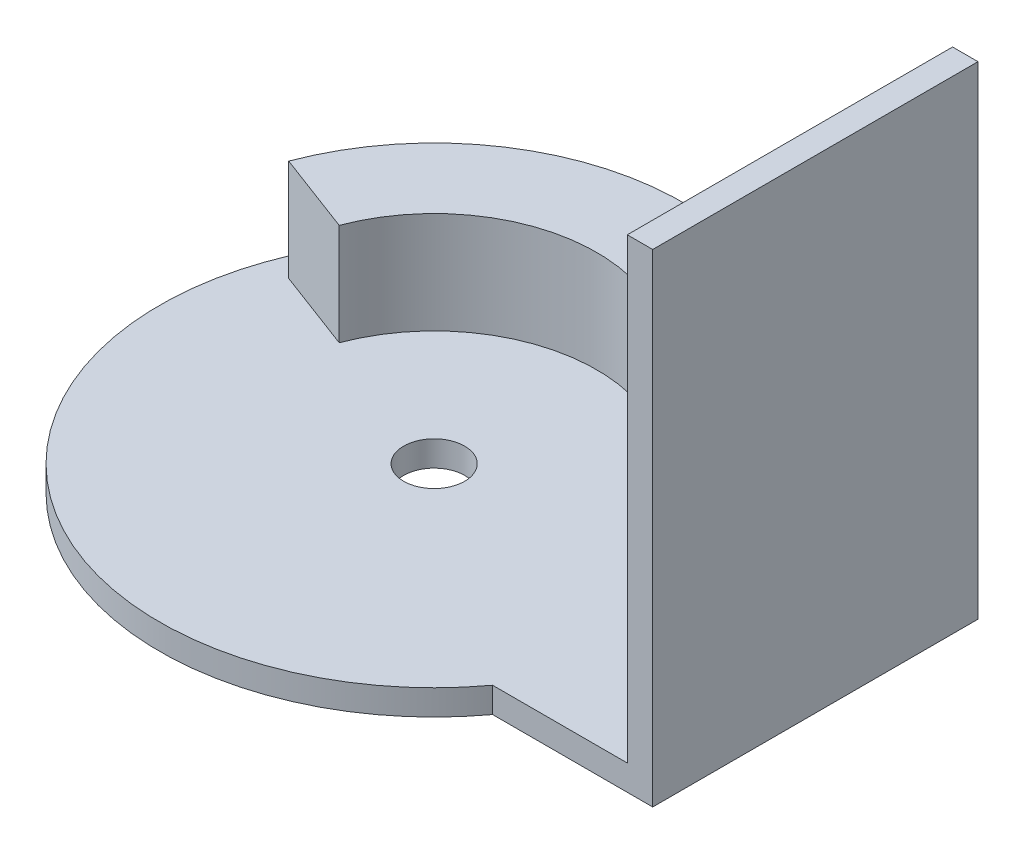
SolidWorks part; units mm, degrees
ref_plane "Front Plane" through (0, 0, 0) normal (0, 0, 1) x (1, 0, 0)
ref_plane "Top Plane" through (0, 0, 0) normal (0, 1, 0) x (1, 0, 0)
ref_plane "Right Plane" through (0, 0, 0) normal (1, 0, 0) x (0, 0, -1)
sketch "Sketch1" plane through (0, 0, 0) normal (0, 1, 0) x (1, 0, 0)
  line L0 (-6.875, 0) -> (6.875, 0) construction
  line L1 (-22.9311, 8.6264) -> (-17.0509, 24.2574) construction
  line L2 (-22.9311, 8.6264) -> (-14.9754, 5.6336)
  line L3 (0, -6.875) -> (0, 6.875) construction
  line L4 (22.9311, 8.6264) -> (14.9754, 5.6336)
  line L5 (-23.9844, 5) -> (23.9844, 5) construction
  circle A0 centre (0, 0) radius 16 construction
  circle A1 centre (0, 0) radius 24.5 construction
  arc A2 (-22.9311, 8.6264) -> (22.9311, 8.6264) centre (0, 0) cw
  arc A3 (-14.9754, 5.6336) -> (14.9754, 5.6336) centre (0, 0) cw
  point P20 (-18.9532, 7.13)
  dimension "D1" = 32
  dimension "D2" = 49
  dimension "D3" = 2.13
  dimension "D4" = 5
extrude "Boss-Extrude1" add sketch "Sketch1" along normal blind 10 contours A2 L4 A3 L2
sketch "Sketch2" plane through (0, 0, 0) normal (0, -1, 0) x (1, 0, 0)
  line L1 (37.5, -16) -> (37.5, 16)
  line L3 (21.7486, -16) -> (37.5, -16)
  line L5 (21.7486, 16) -> (37.5, 16)
  line L6 (0, -23.375) -> (0, 23.375) construction
  circle A1 centre (0, 0) radius 27 construction
  circle A2 centre (0, 0) radius 3
  arc A3 (0, -27) -> (0, 27) centre (0, 0) cw
  circle A4 centre (0, 0) radius 16 construction
  arc A5 (21.7486, -16) -> (0, -27) centre (0, 0) cw
  arc A6 (0, 27) -> (21.7486, 16) centre (0, 0) cw
  dimension "D1" = 54
  dimension "D2" = 6
  dimension "D3" = 37.5
extrude "Boss-Extrude2" add sketch "Sketch2" along normal blind 2.5
sketch "Sketch4" plane through (0, 0, 0) normal (0, 1, 0) x (1, 0, 0)
  line L0 (37.5, -16) -> (21.7486, -16) construction
  line L1 (37.5, -16) -> (35, -16)
  line L2 (37.5, -16) -> (37.5, 16)
  line L3 (37.5, 16) -> (35, 16)
  line L4 (35, -16) -> (35, 16)
  line L5 (21.7486, 16) -> (37.5, 16) construction
  dimension "D1" = 2.5
  dimension "D2" = 35
extrude "Boss-Extrude3" add sketch "Sketch4" along normal blind 45
